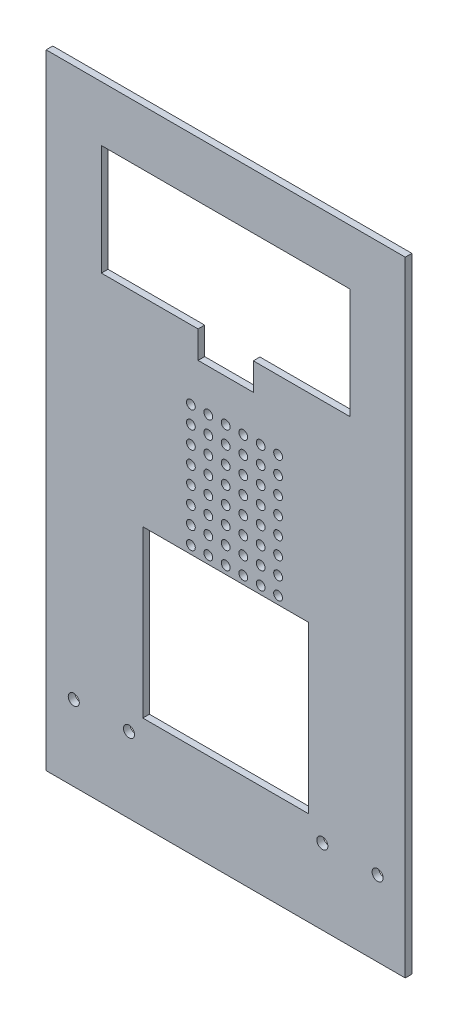
SolidWorks part; units mm, degrees
ref_plane "Front Plane" through (0, 0, 0) normal (0, 0, 1) x (1, 0, 0)
ref_plane "Top Plane" through (0, 0, 0) normal (0, 1, 0) x (1, 0, 0)
ref_plane "Right Plane" through (0, 0, 0) normal (1, 0, 0) x (0, 0, -1)
sketch "Sketch1" plane through (0, 0, 0) normal (0, 0, 1) x (1, 0, 0)
  line L1 (-82.55, 146.05) -> (82.55, 146.05)
  line L2 (-82.55, 146.05) -> (-82.55, -146.05)
  line L3 (-82.55, -146.05) -> (82.55, -146.05)
  line L4 (82.55, 146.05) -> (82.55, -146.05)
  line L5 (-82.55, 146.05) -> (82.55, -146.05) construction
  line L6 (-82.55, -146.05) -> (82.55, 146.05) construction
  point P0 (0, 0)
  dimension "D1" = 165.1
  dimension "D2" = 292.1
extrude "Boss-Extrude1" add sketch "Sketch1" along normal blind 3.048
sketch "Sketch2" plane through (0, 0, 0) normal (0, 0, 1) x (1, 0, 0)
  line L1 (-82.55, -146.05) -> (82.55, -146.05) construction
  line L2 (-82.55, -146.05) -> (82.55, -146.05) construction
  line L3 (8.0869, 109.0549) -> (-8.0869, 109.0549)
  line L4 (8.0869, 109.0549) -> (8.0869, 76.3651)
  line L5 (8.0869, 76.3651) -> (-8.0869, 76.3651)
  line L6 (-8.0869, 109.0549) -> (-8.0869, 76.3651)
  line L7 (8.0869, 109.0549) -> (-8.0869, 76.3651) construction
  line L8 (8.0869, 76.3651) -> (-8.0869, 109.0549) construction
  line L9 (-38.1, -21.59) -> (38.1, -21.59)
  line L10 (-38.1, -21.59) -> (-38.1, -97.79)
  line L11 (-38.1, -97.79) -> (38.1, -97.79)
  line L12 (38.1, -21.59) -> (38.1, -97.79)
  line L13 (-38.1, -21.59) -> (38.1, -97.79) construction
  line L14 (-38.1, -97.79) -> (38.1, -21.59) construction
  circle A1 centre (0, 92.71) radius 10.7315
  circle A2 centre (0, 38.1) radius 2.0193
  circle A3 centre (0, 30.1) radius 2.0193
  circle A4 centre (0, 22.1) radius 2.0193
  circle A5 centre (0, 14.1) radius 2.0193
  circle A6 centre (0, 6.1) radius 2.0193
  circle A7 centre (0, -1.9) radius 2.0193
  circle A8 centre (0, -9.9) radius 2.0193
  circle A9 centre (0, -17.9) radius 2.0193
  circle A10 centre (-8, 38.1) radius 2.0193
  circle A11 centre (-16, 38.1) radius 2.0193
  circle A12 centre (-8, 30.1) radius 2.0193
  circle A13 centre (-16, 30.1) radius 2.0193
  circle A14 centre (-8, 22.1) radius 2.0193
  circle A15 centre (-16, 22.1) radius 2.0193
  circle A16 centre (-8, 14.1) radius 2.0193
  circle A17 centre (-16, 14.1) radius 2.0193
  circle A18 centre (-8, 6.1) radius 2.0193
  circle A19 centre (-16, 6.1) radius 2.0193
  circle A20 centre (-8, -1.9) radius 2.0193
  circle A21 centre (-16, -1.9) radius 2.0193
  circle A22 centre (-8, -9.9) radius 2.0193
  circle A23 centre (-16, -9.9) radius 2.0193
  circle A24 centre (-8, -17.9) radius 2.0193
  circle A25 centre (-16, -17.9) radius 2.0193
  circle A26 centre (24.0869, 14.1) radius 2.0193
  circle A27 centre (8.0869, 14.1) radius 2.0193
  circle A28 centre (8.0869, -17.9) radius 2.0193
  circle A29 centre (24.0869, 6.1) radius 2.0193
  circle A30 centre (16.0869, 6.1) radius 2.0193
  circle A31 centre (8.0869, -1.9) radius 2.0193
  circle A32 centre (8.0869, 30.1) radius 2.0193
  circle A33 centre (24.0869, 22.1) radius 2.0193
  circle A34 centre (24.0869, -1.9) radius 2.0193
  circle A35 centre (24.0869, -9.9) radius 2.0193
  circle A36 centre (8.0869, 6.1) radius 2.0193
  circle A37 centre (16.0869, 22.1) radius 2.0193
  circle A38 centre (8.0869, 22.1) radius 2.0193
  circle A39 centre (8.0869, -9.9) radius 2.0193
  circle A40 centre (24.0869, -17.9) radius 2.0193
  circle A41 centre (16.0869, 14.1) radius 2.0193
  circle A42 centre (16.0869, -17.9) radius 2.0193
  circle A43 centre (16.0869, 30.1) radius 2.0193
  circle A44 centre (24.0869, 30.1) radius 2.0193
  circle A45 centre (16.0869, -9.9) radius 2.0193
  circle A46 centre (16.0869, -1.9) radius 2.0193
  circle A47 centre (16.0869, 38.1) radius 2.0193
  circle A48 centre (8.0869, 38.1) radius 2.0193
  circle A49 centre (24.0869, 38.1) radius 2.0193
  point P2 (0, -59.69)
  dimension "D3" = 21.463
  dimension "D5" = 4.0386
  dimension "D7" = 184.15
  dimension "D2" = 86.36
  dimension "D4" = 152.4
  dimension "D8" = 16.1738
  dimension "D9" = 32.6898
  dimension "D11" = 76.2
  dimension "D12" = 76.2
  dimension "D6" = 3
  dimension "D10" = 8
extrude "Cut-Extrude1" cut sketch "Sketch2" along normal through all contours A13 | A19 | A18 | A20 | A24 | A39 | A31 | L3 L6 L5 L4 | A1 | A3 | A2 | A4 | A5 | A6 | A7 | A8 | A9 | A10 | A12 | A11 | A15 | A14 | A17 | A16 | A21 | A23 | A22 | A25 | L11 L12 L9 L10 | A42 | A40 | A28 | A36 | A27 | A38 | A32 | A48 | A47 | A49 | A43 | A37 | A41 | A30 | A46 | A45 | A35 | A34 | A29 | A26 | A33 | A44 region at (-16, 30.1, 0) region at (-8, 6.1, 0) region at (-16, 6.1, 0) region at (-8, -1.9, 0) region at (-8, -17.9, 0) region at (8.0869, -1.9, 0) region at (8.0869, -9.9, 0)
sketch "Sketch4" plane through (0, 0, 0) normal (0, 0, 1) x (1, 0, 0)
  line L0 (-12.7, 57.3108) -> (-12.7, 69.85)
  line L1 (57.15, 120.65) -> (-57.15, 120.65)
  line L2 (57.15, 120.65) -> (57.15, 69.85)
  line L4 (-57.15, 120.65) -> (-57.15, 69.85)
  line L7 (-12.7, 57.3108) -> (12.7, 57.3108)
  line L9 (12.7, 57.3108) -> (12.7, 69.85)
  line L10 (-57.15, 69.85) -> (-12.7, 69.85)
  line L11 (12.7, 69.85) -> (57.15, 69.85)
  line L12 (82.55, 146.05) -> (-82.55, 146.05) construction
  circle A0 centre (0, -1.9) radius 2.0193 construction
  point P5 (0, 146.05)
  point P11 (0, 0)
  point P12 (0, 120.65)
  dimension "D1" = 12.5392
  dimension "D2" = 114.3
  dimension "D3" = 25.4
  dimension "D4" = 25.4
  dimension "D6" = 59.2108
extrude "Cut-Extrude2" cut sketch "Sketch4" along normal through all
sketch "Sketch5" plane through (0, 0, 0) normal (0, 0, -1) x (-1, 0, 0)
  line L0 (82.55, -146.05) -> (-82.55, -146.05) construction
  line L1 (-82.55, -146.05) -> (-82.55, 146.05) construction
  line L2 (0, 1.6764) -> (0, -1.6764) construction
  circle A0 centre (-44.45, -106.299) radius 2.54
  circle A2 centre (-69.85, -106.299) radius 2.54
  circle A3 centre (69.85, -106.299) radius 2.54
  circle A4 centre (44.45, -106.299) radius 2.54
  dimension "D1" = 5.08
  dimension "D2" = 39.751
  dimension "D3" = 25.4
  dimension "D4" = 12.7
extrude "Cut-Extrude3" cut sketch "Sketch5" against normal through all
sketch "Sketch6" plane through (0, 0, 0) normal (0, 0, -1) x (-1, 0, 0)
  line L0 (82.55, 146.05) -> (82.55, -146.05) construction
  line L1 (-82.55, -146.05) -> (82.55, -146.05)
  line L2 (-82.55, -146.05) -> (-82.55, -140.97)
  line L3 (-82.55, -140.97) -> (82.55, -140.97)
  line L4 (82.55, -146.05) -> (82.55, -140.97)
  dimension "D1" = 5.08
extrude "Cut-Extrude4" cut sketch "Sketch6" against normal through all
equation "\"thickness_acrylic0.1\"=0.1in"
equation "\"motor offset\"=6mm"
equation "\"thickness0.25\"=0.225in"
equation "\"thickness0.125\"=0.122in"
